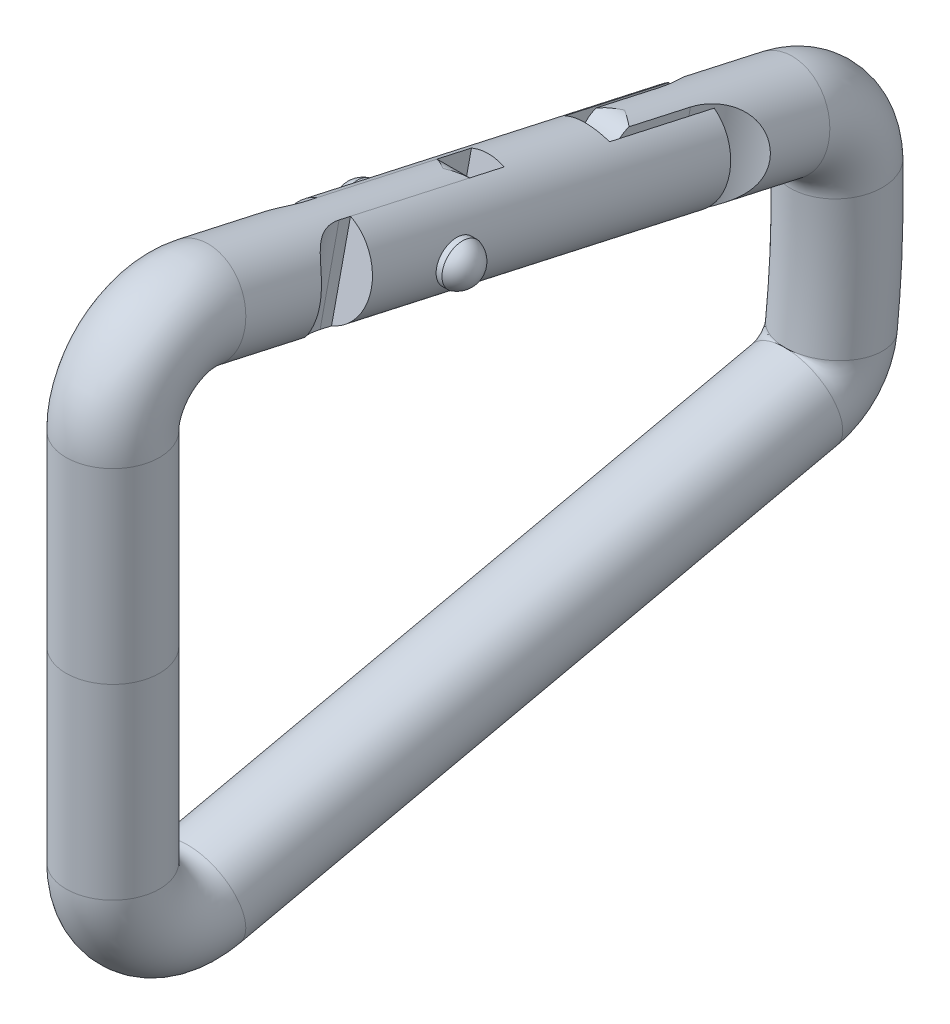
SolidWorks part; units mm, degrees
ref_plane "Front Plane" through (0, 0, 0) normal (0, 0, 1) x (1, 0, 0)
ref_plane "Top Plane" through (0, 0, 0) normal (0, 1, 0) x (1, 0, 0)
ref_plane "Right Plane" through (0, 0, 0) normal (1, 0, 0) x (0, 0, -1)
sketch "Sketch1" plane through (0, 0, 0) normal (1, 0, 0) x (0, 0, -1)
  line L0 (-91.2812, 0) -> (91.2813, 0) construction
  line L1 (-91.2812, 12.7) -> (42.0687, 12.7) construction
  line L2 (42.0687, 12.7) -> (42.0687, -12.7) construction
  line L3 (42.0687, -12.7) -> (-91.2812, -12.7) construction
  line L7 (-91.2812, -12.7) -> (-91.2812, 0) construction
  line L10 (45.3742, -20.4493) -> (85.9441, -11.4552) construction
  line L14 (85.0645, 11.6502) -> (45.3742, 20.4493) construction
  line L15 (35.7187, -12.7) -> (35.7187, 12.7) construction
  line L17 (42.0687, -12.7) -> (42.0687, 12.7) construction
  line L18 (43.9998, -14.2499) -> (84.5697, -5.2558) construction
  line L19 (83.6901, 5.4507) -> (43.9998, 14.2499) construction
  line L20 (84.3773, 8.5505) -> (44.687, 17.3496) construction
  line L21 (38.8937, -12.7) -> (38.8937, 12.7) construction
  line L22 (44.687, -17.3496) -> (85.2569, -8.3555) construction
  line L23 (62.932, 16.5569) -> (72.2312, 14.4953) construction
  line L24 (-91.2812, 0) -> (-91.2812, 12.7) construction
  arc A3 (45.3742, 20.4493) -> (35.7187, 12.7) centre (43.6562, 12.7) ccw construction
  arc A4 (45.3742, -20.4493) -> (35.7187, -12.7) centre (43.6562, -12.7) cw construction
  arc A5 (85.0645, 11.6502) -> (91.2812, 4.1105) centre (83.3465, 3.9009) cw construction
  arc A6 (91.2812, 4.1105) -> (90.8844, -5.9243) centre (15.1078, 2.0979) cw construction
  arc A7 (90.8844, -5.9243) -> (85.9441, -11.4552) centre (84.5697, -5.2558) cw construction
  arc A8 (43.9998, 14.2499) -> (42.0687, 12.7) centre (43.6562, 12.7) ccw construction
  arc A9 (43.9998, -14.2499) -> (42.0687, -12.7) centre (43.6562, -12.7) cw construction
  arc A10 (84.5697, -5.2558) -> (84.5697, -5.2558) centre (84.5697, -5.2558) cw construction
  arc A11 (84.9335, 3.9428) -> (84.5697, -5.2558) centre (15.1078, 2.0979) cw construction
  arc A12 (83.6901, 5.4507) -> (84.9335, 3.9428) centre (83.3465, 3.9009) cw construction
  arc A13 (44.687, 17.3496) -> (38.8937, 12.7) centre (43.6562, 12.7) ccw construction
  arc A14 (44.687, -17.3496) -> (38.8937, -12.7) centre (43.6562, -12.7) cw construction
  arc A15 (87.727, -5.59) -> (85.2569, -8.3555) centre (84.5697, -5.2558) cw construction
  arc A16 (88.1074, 4.0267) -> (87.727, -5.59) centre (15.1078, 2.0979) cw construction
  arc A17 (84.3773, 8.5505) -> (88.1074, 4.0267) centre (83.3465, 3.9009) cw construction
  point P4 (0, 0)
  point P13 (42.0687, 0)
  point P14 (35.7187, 0)
  point P15 (91.2813, 0)
  point P16 (62.932, 16.5569)
  point P28 (72.2312, 14.4953)
  point P30 (-91.2812, 12.7)
  point P33 (38.8937, 0)
  point P34 (67.5816, 15.5261)
  dimension "D6" = 7.9375
  dimension "D5" = 6.35
  dimension "D7" = 7.9375
  dimension "D8" = 76.2
  dimension "D12" = 19.05
  dimension "D14" = 0.3969
  dimension "Length" = 182.5625
  dimension "Width" = 25.4
  dimension "D2" = 12.5
  dimension "D3" = 12.5
  dimension "Carabiner Length" = 55.5625
  dimension "D11" = 3.175
  dimension "Hook Opening Width" = 9.525
  dimension "D9" = 6.35
  dimension "D10" = 3.175
sketch "Sketch2" plane through (0, 0, 0) normal (0, 1, 0) x (1, 0, 0)
  line L0 (-0.0254, 0) -> (-3.0734, 0) construction
  dimension "D1" = 0.0254
  dimension "Thickness" = 3.048
sketch "Sketch3" plane through (0, 0, 0) normal (0, 1, 0) x (1, 0, 0)
  line L0 (0, 44.687) -> (0, 85.2569) construction
  circle A0 centre (0, 38.8937) radius 3.175
sketch "Sketch4" plane through (0, 0, 0) normal (1, 0, 0) x (0, 0, -1)
  line L0 (44.687, 17.3496) -> (84.3773, 8.5505)
  line L2 (85.2569, -8.3555) -> (44.687, -17.3496)
  line L4 (38.8937, -12.7) -> (38.8937, 12.7)
  arc A0 (38.8937, 12.7) -> (44.687, 17.3496) centre (43.6562, 12.7) cw
  arc A1 (84.3773, 8.5505) -> (88.1074, 4.0267) centre (83.3465, 3.9009) cw
  arc A2 (88.1074, 4.0267) -> (87.727, -5.59) centre (15.1078, 2.0979) cw
  arc A3 (87.727, -5.59) -> (85.2569, -8.3555) centre (84.5697, -5.2558) cw
  arc A4 (44.687, -17.3496) -> (38.8937, -12.7) centre (43.6562, -12.7) cw
sweep "Sweep1" add profiles "Sketch3" path "Sketch4"
sketch "Sketch5" plane through (0, 0, 0) normal (1, 0, 0) x (0, 0, -1)
  line L0 (61.3262, 16.9129) -> (73.6763, 14.1749)
  line L1 (85.0645, 11.6502) -> (45.3742, 20.4493) construction
  line L3 (83.6901, 5.4507) -> (43.9998, 14.2499) construction
  line L4 (74.0915, 7.5787) -> (58.1622, 11.1102)
  line L5 (59.6762, 11.5875) -> (62.153, 14.2905)
  line L6 (72.9211, 8.6512) -> (71.8187, 12.1477)
  line L7 (84.3773, 8.5505) -> (44.687, 17.3496) construction
  line L8 (62.1889, 13.4696) -> (62.5325, 15.0194) construction
  line L9 (62.5325, 15.0194) -> (71.7452, 12.6251) construction
  line L10 (72.2312, 14.4953) -> (71.7452, 12.6251) construction
  line L11 (62.932, 16.5569) -> (62.5325, 15.0194) construction
  arc A0 (58.1622, 11.1102) -> (59.6762, 11.5875) centre (58.5057, 12.66) ccw
  arc A1 (61.3262, 16.9129) -> (62.153, 14.2905) centre (60.9826, 15.363) cw
  arc A2 (74.0915, 7.5787) -> (72.9211, 8.6512) centre (74.4351, 9.1286) cw
  arc A3 (73.6763, 14.1749) -> (71.8187, 12.1477) centre (73.3327, 12.6251) ccw
  circle A4 centre (59.0891, 14.1567) radius 0.7937
  dimension "D3" = 1.5875
  dimension "D5" = 1.5875
  dimension "D2" = 60
  dimension "D6" = 3.175
extrude "Cut-Extrude1" cut sketch "Sketch5" against normal through all both and the other way through all
ref_plane "Plane1" through (0, 25.9796, -5.7595) normal (0, 0.9763, -0.2164) x (0, 0.2164, 0.9763)
sketch "Sketch6" plane through (0, 25.9796, -5.7595) normal (0, 0.9763, -0.2164) x (0, 0.2164, 0.9763)
  line L0 (-57.7994, 1.1112) -> (-57.7994, 3.175)
  line L1 (-57.7994, 2.7496) -> (-57.7994, -2.7496) construction
  line L2 (-47.3829, 3.175) -> (-85.0444, 3.175) construction
  line L3 (-57.7994, 3.175) -> (-45.0994, 3.175)
  line L4 (-39.8726, 3.175) -> (-53.8306, 3.175) construction
  line L6 (-47.8934, 1.1112) -> (-57.7994, 1.1112)
  line L7 (-57.7994, -1.1112) -> (-57.7994, -3.175)
  line L8 (-85.0444, -3.175) -> (-47.3829, -3.175) construction
  line L9 (-57.7994, -3.175) -> (-45.0994, -3.175)
  line L10 (-53.8306, -3.175) -> (-39.8726, -3.175) construction
  line L12 (-47.8934, -1.1112) -> (-57.7994, -1.1112)
  line L13 (-67.2743, 1.1112) -> (-67.2743, 3.175)
  line L14 (-67.2743, -2.7496) -> (-67.2743, 2.7496) construction
  line L15 (-67.2743, 3.175) -> (-76.4183, 3.175)
  line L16 (-67.9453, 3.175) -> (-80.5266, 3.175) construction
  line L18 (-72.3543, 1.1112) -> (-67.2743, 1.1112)
  line L19 (-67.2743, -1.1112) -> (-67.2743, -3.175)
  line L20 (-85.0444, -3.175) -> (-47.3829, -3.175) construction
  line L21 (-67.2743, -3.175) -> (-76.4183, -3.175)
  line L22 (-80.5266, -3.175) -> (-67.9453, -3.175) construction
  line L24 (-72.3543, -1.1112) -> (-67.2743, -1.1112)
  arc A0 (-47.8934, 1.1112) -> (-45.0994, 3.175) centre (-47.8934, 4.0344) ccw
  arc A1 (-47.8934, -1.1112) -> (-45.0994, -3.175) centre (-47.8934, -4.0344) cw
  arc A2 (-72.3543, 1.1112) -> (-76.4183, 3.175) centre (-72.3543, 6.1446) cw
  arc A3 (-72.3543, -1.1112) -> (-76.4183, -3.175) centre (-72.3543, -6.1446) ccw
  dimension "D2" = 12.7
  dimension "D1" = 2.2225
  dimension "D3" = 9.906
  dimension "D4" = 2.2225
  dimension "D5" = 9.144
  dimension "D6" = 5.08
extrude "Cut-Extrude2" cut sketch "Sketch6" against normal mid plane 7.3025
sketch "Sketch7" plane through (0, 25.9796, -5.7595) normal (0, 0.9763, -0.2164) x (0, 0.2164, 0.9763)
  line L0 (-73.6243, 3.175) -> (-73.6243, -3.175)
  line L1 (-47.3829, 3.175) -> (-85.0444, 3.175) construction
  line L2 (-85.0444, -3.175) -> (-47.3829, -3.175) construction
  line L3 (-73.6243, -3.175) -> (-48.6871, -3.175)
  line L5 (-48.6871, 3.175) -> (-73.6243, 3.175)
  line L6 (-67.2743, -1.1112) -> (-67.2743, 1.1112) construction
  line L8 (-48.6871, 3.175) -> (-48.6871, 1.1112)
  line L9 (-56.9847, 1.1112) -> (-47.8934, 1.1113) construction
  line L10 (-48.6871, 1.1112) -> (-59.3869, 1.1112)
  line L11 (-59.3869, 1.1112) -> (-59.3869, -1.1112)
  line L12 (-59.3869, -1.1112) -> (-48.6871, -1.1112)
  line L13 (-47.8934, -1.1112) -> (-56.9847, -1.1112) construction
  line L14 (-48.6871, -1.1112) -> (-48.6871, -3.175)
  dimension "D1" = 6.35
  dimension "D2" = 1.5875
  dimension "D3" = 0.7937
extrude "Boss-Extrude1" add sketch "Sketch7" against normal up to vertex (3.175 mm away) from vertex separate body up to point (0, 11.1102, -58.1622) starting at point (0, 16.9129, -61.3262)
sketch "Sketch8" plane through (0, 0, 0) normal (1, 0, 0) x (0, 0, -1)
  circle A0 centre (59.0891, 14.1567) radius 0.7937
  circle A1 centre (59.0891, 14.1567) radius 0.7937 construction
extrude "Cut-Extrude3" cut sketch "Sketch8" against normal through all both and the other way through all
sketch "Sketch9" plane through (0, 0, 0) normal (1, 0, 0) x (0, 0, -1)
  line L0 (78.3259, 13.1441) -> (76.9515, 6.9447)
  line L1 (76.9515, 6.9447) -> (73.1967, 7.7771)
  line L2 (83.6901, 5.4507) -> (43.9998, 14.2499) construction
  line L3 (73.1967, 7.7771) -> (70.9918, 14.7701)
  line L4 (85.0645, 11.6502) -> (45.3742, 20.4493) construction
  line L5 (70.9918, 14.7701) -> (78.3259, 13.1441)
  line L6 (72.9211, 8.6512) -> (71.8187, 12.1477) construction
extrude "Cut-Extrude4" cut sketch "Sketch9" against normal mid plane 3.048
sketch "Sketch10" plane through (0, -10.5378, -47.5331) normal (0, 0.2164, 0.9763) x (1, 0, 0)
  line L0 (0, 23.77) -> (0, 29.7854) construction
  line L1 (0, 23.0011) -> (0, 26.6104) construction
  line L2 (-1.1112, 29.7854) -> (1.1112, 29.7854) construction
  line L3 (-1.1112, 23.4354) -> (1.1112, 23.4354) construction
  line L5 (-3.81, 30.4204) -> (3.81, 30.4204)
  line L6 (-3.81, 30.4204) -> (-3.81, 22.8004)
  line L7 (-3.81, 22.8004) -> (3.81, 22.8004)
  line L8 (3.81, 30.4204) -> (3.81, 22.8004)
  circle A0 centre (0, 26.6104) radius 3.175
  point P15 (0, 30.4204)
  point P16 (3.81, 26.6104)
  dimension "D1" = 7.62
extrude "Cut-Extrude5" cut sketch "Sketch10" against normal up to surface (24.9372 mm away) up to face at (2.3495, 10.0444, -77.6387)
ref_axis "Axis1" through (-3.175, 14.1567, -59.0891) along (1, 0, 0)
sketch "Sketch11" plane through (0, 25.9796, -5.7595) normal (0, 0.9763, -0.2164) x (0, 0.2164, 0.9763)
  line L0 (-55.4181, 3.175) -> (-55.4181, -3.175)
  line L1 (-55.4181, -3.175) -> (-56.0214, -3.175)
  line L2 (-73.6243, -3.175) -> (-55.4181, -3.175) construction
  line L5 (-54.6244, -3.175) -> (-54.6244, -1.1112) construction
  line L6 (-54.6244, -4.6355) -> (-54.6244, 4.6355)
  line L9 (-55.4181, 3.175) -> (-73.6243, 3.175) construction
  line L10 (-56.0214, 3.175) -> (-55.4181, 3.175)
  line L11 (-56.0214, 3.175) -> (-56.0214, 3.5719)
  line L12 (-56.0214, -3.175) -> (-56.0214, -3.5719)
  arc A0 (-54.6244, 4.6355) -> (-56.0214, 3.5719) centre (-54.6244, 3.1863) ccw
  arc A1 (-54.6244, -4.6355) -> (-56.0214, -3.5719) centre (-54.6244, -3.1863) cw
  dimension "D1" = 0.3969
  dimension "D2" = 1.397
  dimension "D3" = 9.271
revolve "Revolve1" add sketch "Sketch11" angle 360 about L6
